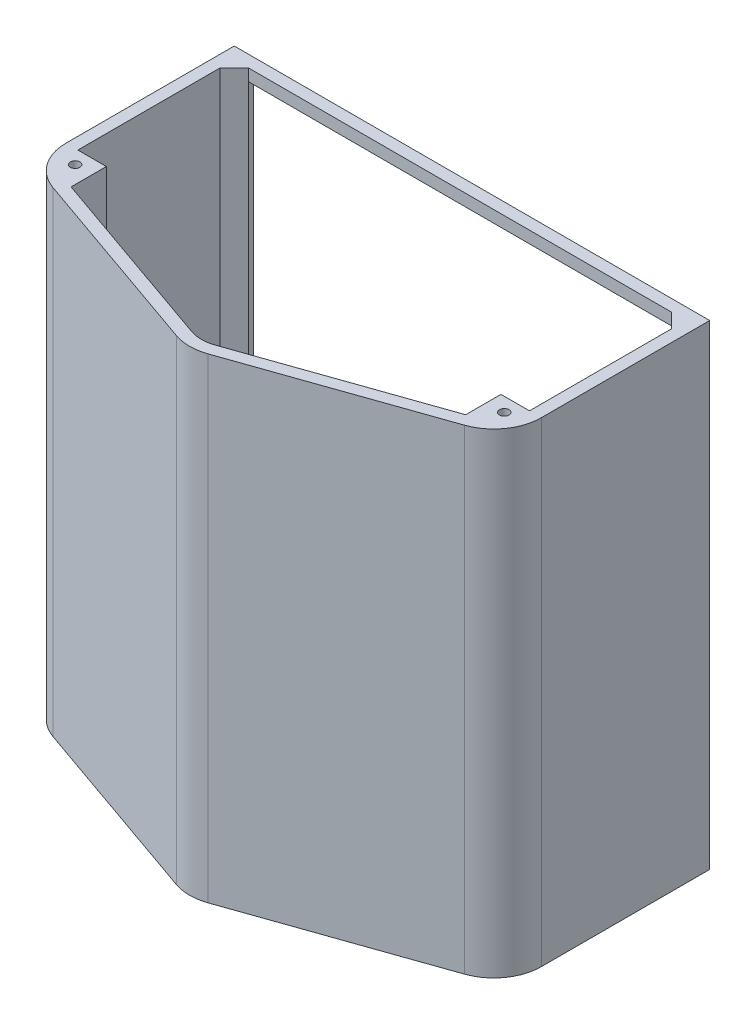
SolidWorks part; units mm, degrees
ref_plane "Front Plane" through (0, 0, 0) normal (0, 0, 1) x (1, 0, 0)
ref_plane "Top Plane" through (0, 0, 0) normal (0, 1, 0) x (1, 0, 0)
ref_plane "Right Plane" through (0, 0, 0) normal (1, 0, 0) x (0, 0, -1)
sketch "Sketch1" plane through (0, 0, 0) normal (0, 1, 0) x (1, 0, 0)
  line L0 (0, 0) -> (200, 0)
  line L1 (200, 0) -> (200, -70.8104)
  line L2 (0, 0) -> (0, -70.8104)
  line L4 (13.393, -89.6875) -> (93.393, -117.6875)
  line L5 (186.607, -89.6875) -> (106.607, -117.6875)
  arc A0 (93.393, -117.6875) -> (106.607, -117.6875) centre (100, -98.8104) ccw
  arc A1 (200, -70.8104) -> (186.607, -89.6875) centre (180, -70.8104) cw
  arc A2 (13.393, -89.6875) -> (0, -70.8104) centre (20, -70.8104) cw
  point P12 (200, -85)
  point P15 (0, -85)
  dimension "D5" = 20
  dimension "D1" = 200
  dimension "D2" = 85
  dimension "D3" = 85
extrude "Boss-Extrude1" add sketch "Sketch1" along normal blind 200 contours L2 A2 L4 A0 L5 A1 L1 L0
shell "Shell3" thickness 5 removed face at (100, 0, 70.2203) removed face at (100, 200, 70.2203)
sketch "Sketch2" plane through (0, 0, 0) normal (0, 1, 0) x (1, 0, 0)
  line L0 (195, 0) -> (187.4587, 0)
  line L1 (0, 0) -> (200, 0) construction
  line L2 (189, -3) -> (189, -5)
  line L3 (5, -5) -> (195, -5) construction
  line L4 (189, -5) -> (11, -5)
  line L6 (12.3079, 0) -> (5, 0)
  line L7 (5, 0) -> (5, -3)
  line L8 (5, -3) -> (11, -3)
  line L9 (12.3079, 0) -> (187.4587, 0)
  line L10 (189, -3) -> (195, -3)
  line L11 (195, -3) -> (195, 0)
  line L12 (11, -3) -> (11, -5)
  dimension "D1" = 3
  dimension "D2" = 6
  dimension "D3" = 3
  dimension "D4" = 6
extrude "Cut-Extrude1" cut sketch "Sketch2" along normal blind 195
sketch "Sketch3" plane through (0, 0, 0) normal (0, 1, 0) x (1, 0, 0)
  line L0 (5, -5) -> (5, -11)
  line L1 (5, -5) -> (5, -70.8104) construction
  line L2 (5, -11) -> (11, -5)
  line L3 (5, -5) -> (195, -5) construction
  line L4 (11, -5) -> (5, -5)
  line L5 (195, -5) -> (195, -11)
  line L6 (195, -5) -> (195, -70.8104) construction
  line L7 (195, -11) -> (189, -5)
  line L8 (189, -5) -> (195, -5)
  dimension "D1" = 6
  dimension "D2" = 6
  dimension "D3" = 6
  dimension "D4" = 6
extrude "Boss-Extrude2" add sketch "Sketch3" along normal blind 200
sketch "Sketch4" plane through (0, 0, 0) normal (0, 1, 0) x (1, 0, 0)
  line L0 (5, -70.8104) -> (17, -70.8104)
  line L1 (17, -70.8104) -> (17, -85.6526)
  line L2 (15.0447, -84.9683) -> (95.0447, -112.9683) construction
  line L3 (13.393, -89.6875) -> (0, -70.8104)
  line L4 (5, -70.8104) -> (0, -70.8104)
  line L5 (195, -70.8104) -> (183, -70.8104)
  line L8 (186.607, -89.6875) -> (200, -70.8104)
  line L9 (200, -70.8104) -> (195, -70.8104)
  line L10 (17, -85.6526) -> (13.393, -89.6875)
  line L11 (183, -70.8104) -> (183, -85.6526)
  line L12 (184.9553, -84.9683) -> (104.9553, -112.9683) construction
  line L13 (183, -85.6526) -> (186.607, -89.6875)
  dimension "D1" = 12
  dimension "D2" = 14.8422
  dimension "D3" = 12
  dimension "D4" = 14.8422
extrude "Boss-Extrude3" add sketch "Sketch4" along normal blind 200
sketch "Sketch5" plane through (0, 0, 0) normal (0, 1, 0) x (1, 0, 0)
  line L2 (9.7435, -76.6773) -> (11, -78.2315)
  line L4 (195, -70.8104) -> (183, -70.8104)
  line L6 (190.2565, -76.6773) -> (189, -78.2315)
  circle A0 centre (9.7435, -76.6773) radius 1.9986
  circle A1 centre (190.2565, -76.6773) radius 1.9986
  dimension "D2" = 1.9986
  dimension "D1" = 1.9986
extrude "Cut-Extrude2" cut sketch "Sketch5" along normal blind 210 contours A1 | A0
